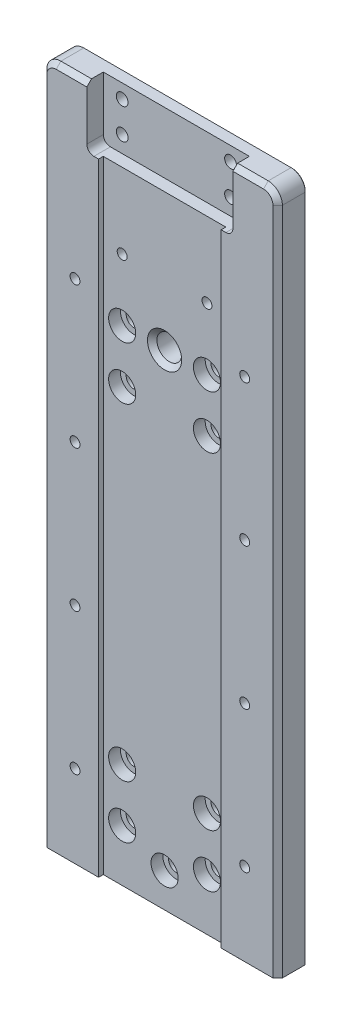
SolidWorks part; units mm, degrees
material "1060 Alloy"
ref_plane "Front Plane" through (0, 0, 0) normal (0, 0, 1) x (1, 0, 0)
ref_plane "Top Plane" through (0, 0, 0) normal (0, 1, 0) x (1, 0, 0)
ref_plane "Right Plane" through (0, 0, 0) normal (1, 0, 0) x (0, 0, -1)
sketch "Sketch1" plane through (0, 0, 0) normal (0, 0, 1) x (1, 0, 0)
  line L1 (50, -145) -> (-50, -145)
  line L2 (50, -145) -> (50, 145)
  line L3 (50, 145) -> (-50, 145)
  line L4 (-50, -145) -> (-50, 145)
  line L5 (50, -145) -> (-50, 145) construction
  line L6 (50, 145) -> (-50, -145) construction
  point P0 (0, 0)
  dimension "D1" = 100
  dimension "D2" = 290
extrude "Boss-Extrude1" add sketch "Sketch1" along normal mid plane 12
sketch "Sketch2" plane through (0, 0, 6) normal (0, 0, 1) x (1, 0, 0)
  line L0 (0, 132) -> (0, 0) construction
  line L1 (31, 119) -> (-31, 119)
  line L2 (31, 119) -> (31, 145)
  line L3 (31, 145) -> (-31, 145)
  line L4 (-31, 119) -> (-31, 145)
  line L5 (31, 119) -> (-31, 145) construction
  line L6 (31, 145) -> (-31, 119) construction
  line L7 (50, 145) -> (-50, 145) construction
  point P0 (0, 132)
  dimension "D1" = 62
  dimension "D2" = 26
extrude "Cut-Extrude1" cut sketch "Sketch2" against normal blind 7
sketch "Sketch3" plane through (0, 0, 6) normal (0, 0, 1) x (1, 0, 0)
  line L0 (-50, -145) -> (50, -145) construction
  line L1 (26, 145) -> (-26, 145)
  line L2 (26, 145) -> (26, -145)
  line L3 (26, -145) -> (-26, -145)
  line L4 (-26, 145) -> (-26, -145)
  line L5 (26, 145) -> (-26, -145) construction
  line L6 (26, -145) -> (-26, 145) construction
  point P0 (0, 0)
  dimension "D1" = 52
extrude "Cut-Extrude2" cut sketch "Sketch3" against normal blind 2
sketch "Sketch4" plane through (0, 0, -6) normal (0, 0, 1) x (1, 0, 0)
  line L0 (0, 132.5) -> (0, 0) construction
  line L1 (23, 126) -> (-23, 126) construction
  line L2 (23, 126) -> (23, 139) construction
  line L3 (23, 139) -> (-23, 139) construction
  line L4 (-23, 126) -> (-23, 139) construction
  line L5 (23, 126) -> (-23, 139) construction
  line L6 (23, 139) -> (-23, 126) construction
  line L7 (31, 145) -> (-31, 145) construction
  line L8 (-18, 87.065) -> (-18, 38.265) construction
  line L9 (-36, 145) -> (-36, -110) construction
  line L10 (-31, 145) -> (-50, 145) construction
  line L11 (-50, -145) -> (-26, -145) construction
  line L12 (0, 0) -> (0, -145) construction
  line L13 (-26, -145) -> (26, -145) construction
  line L14 (50, 26.265) -> (-50, 26.265) construction
  line L15 (18, -100.475) -> (-18, -100.475) construction
  line L16 (18, -100.475) -> (18, -122.975) construction
  line L17 (18, -122.975) -> (-18, -122.975) construction
  line L18 (-18, -100.475) -> (-18, -122.975) construction
  line L19 (18, -100.475) -> (-18, -122.975) construction
  line L20 (18, -122.975) -> (-18, -100.475) construction
  line L21 (50, 26.265) -> (50, 77.065) construction
  line L22 (50, 77.065) -> (-50, 77.065) construction
  line L23 (-50, 26.265) -> (-50, 77.065) construction
  line L24 (50, 26.265) -> (-50, 77.065) construction
  line L25 (50, 77.065) -> (-50, 26.265) construction
  circle A0 centre (-23, 139) radius 2.5
  circle A1 centre (23, 139) radius 2.5
  circle A2 centre (23, 126) radius 2.5
  circle A3 centre (-23, 126) radius 2.5
  circle A4 centre (0, 60.765) radius 5.25
  circle A5 centre (-18, 87.065) radius 2.1
  circle A6 centre (-18, 60.765) radius 3.3
  circle A7 centre (-18, 38.265) radius 3.3
  circle A9 centre (-36, 70) radius 2.1
  circle A10 centre (-36, 58.75) radius 2.1 construction
  circle A11 centre (-36, 10) radius 2.1
  circle A12 centre (-36, -110) radius 2.1
  circle A13 centre (-36, -50) radius 2.1
  circle A14 centre (-18, -100.475) radius 3.3
  circle A15 centre (-18, -122.975) radius 3.3
  circle A16 centre (18, -100.475) radius 3.3
  circle A17 centre (18, -122.975) radius 3.3
  circle A18 centre (0, -130.475) radius 3.3
  circle A20 centre (36, 70) radius 2.1
  circle A21 centre (36, 58.75) radius 2.1 construction
  circle A22 centre (18, 87.065) radius 2.1
  circle A23 centre (18, 38.265) radius 3.3
  circle A24 centre (18, 60.765) radius 3.3
  circle A25 centre (36, 10) radius 2.1
  circle A26 centre (36, -50) radius 2.1
  circle A27 centre (36, -110) radius 2.1
  point P0 (0, 132.5)
  point P36 (0, -111.725)
  point P68 (0, 51.665)
  dimension "D1" = 5
  dimension "D5" = 10.5
  dimension "D12" = 4.2
  dimension "D19" = 6.6
  dimension "D9" = 6.6
  dimension "D2" = 13
  dimension "D3" = 46
  dimension "D4" = 6
  dimension "D8" = 18
  dimension "D10" = 22.5
  dimension "D11" = 36
  dimension "D13" = 35
  dimension "D14" = 60
  dimension "D15" = 60
  dimension "D16" = 48.75
  dimension "D17" = 11.25
  dimension "D20" = 14.525
  dimension "D21" = 36
  dimension "D23" = 22.5
  dimension "D24" = 100
  dimension "D25" = 50.8
  dimension "D7" = 10
  dimension "D6" = 12
  dimension "D18" = 171.265
  dimension "D22" = 7.5
extrude "Cut-Extrude HOLES" cut sketch "Sketch4" along normal blind 21
fillet "Fillet1" radius 3 2 edges at (31, 119, 2.5) (-31, 119, 2.5)
fillet "Fillet2" radius 6 2 edges at (50, 145, 0) (-50, 145, 0)
chamfer "Chamfer1" distance 2 angle 45 6 edges at (50, -3, 6) (48.2426, 143.2426, 6) (37.5, 145, 6) (-50, -3, 6) (-48.2426, 143.2426, 6) (-37.5, 145, 6)
sketch "Sketch5" plane through (0, 0, 4) normal (0, 0, 1) x (1, 0, 0)
  circle A1 centre (-18, 60.765) radius 5.75
  circle A2 centre (-18, 38.265) radius 5.75
  circle A3 centre (18, 38.265) radius 5.75
  circle A4 centre (18, 60.765) radius 5.75
  circle A6 centre (18, -100.475) radius 5.75
  circle A7 centre (-18, -100.475) radius 5.75
  circle A8 centre (-18, -122.975) radius 5.75
  circle A9 centre (0, -130.475) radius 5.75
  circle A10 centre (18, -122.975) radius 5.75
  dimension "D1" = 11.5
extrude "Cut-Extrude5" cut sketch "Sketch5" against normal blind 5
chamfer "Chamfer2" distance 2 angle 45 1 edges at (-5.25, 60.765, 4)
chamfer "Chamfer3" distance 0.3 angle 45 5 edges at (-50, -3, -6) (-48.2426, 143.2426, -6) (48.2426, 143.2426, -6) (50, -3, -6) (0, 145, -6)
equation "\"M5_tap\"=4.2mm       ' Below you can do mesurements as follows: cm, mm, ft, in, m, "
equation "\"M5_clearence\"=5.5mm"
equation "\"M6_tap\"=5mm"
equation "\"M6_clearence\"=6.6mm"
equation "\"D1@Sketch4\"=\"M6_tap\""
equation "\"D12@Sketch4\"=\"M5_tap\""
equation "\"D19@Sketch4\"=\"M6_clearence\""
equation "\"work_area_width\"=1100mm"
equation "\"work_area_depth\"=900mm"
equation "\"steel_base_width\"=3in "
equation "\"steel_base_height\"=2in"
equation "\"steel_base_wall_thickness\"=0.125in"
equation "\"steel_base_radius\"=6mm"
equation "\"steel_sides_width\"=3in     'this tube is rotated so flip width/height"
equation "\"steel_sides_height\"=2in    'this tube is rotated so flip width/height"
equation "\"steel_sides_wall_thickness\"=0.125in"
equation "\"steel_sides_radius\"=6mm"
equation "\"steel_gantry_width\"=4in    'this tube is rotated so flip width/height"
equation "\"steel_gantry_height\"=3in    'this tube is rotated so flip width/height"
equation "\"steel_gantry_wall_thickness\"=0.125in"
equation "\"steel_gantry_radius\"=6mm"
equation "\"steel_rollers_width\"=3in"
equation "\"steel_rollers_height\"=2in    'keep as low as possible as this increases how big plastic parts are"
equation "\"steel_rollers_wall_thickness\"=0.125in"
equation "\"steel_rollers_radius\"=6mm"
equation "\"steel_zbox_width\"=4in     'if the gantry height (rotated) is too thick, a wider zbox is necessary"
equation "\"steel_zbox_height\"=2in     'hole patteren changes as the zbox and gantry height (rotated) changes."
equation "\"steel_zbox_wall_thickness\"=0.125in"
equation "\"steel_zbox_radius\"=6mm"
equation "\"alu_zangle_width\"=3.5in     'check that it doesn't interfer with the gantry"
equation "\"alu_zangle_height\"=2in"
equation "\"alu_zangle_wall_thickness\"=0.375in   'check that it doesn't interfer with the gantry"
equation "\"D9@Sketch4\"=\"M6_clearence\""
equation "\"D25@Sketch4\"=\"steel_zbox_height\""
equation "\"D6@Sketch4\"=\"steel_zbox_radius\"*2"
equation "\"D18@Sketch4\"=\"steel_gantry_width\" + \"alu_zangle_wall_thickness\" + 60.14"
equation "\"D20@Sketch4\"=\"alu_zangle_wall_thickness\" + 5"
